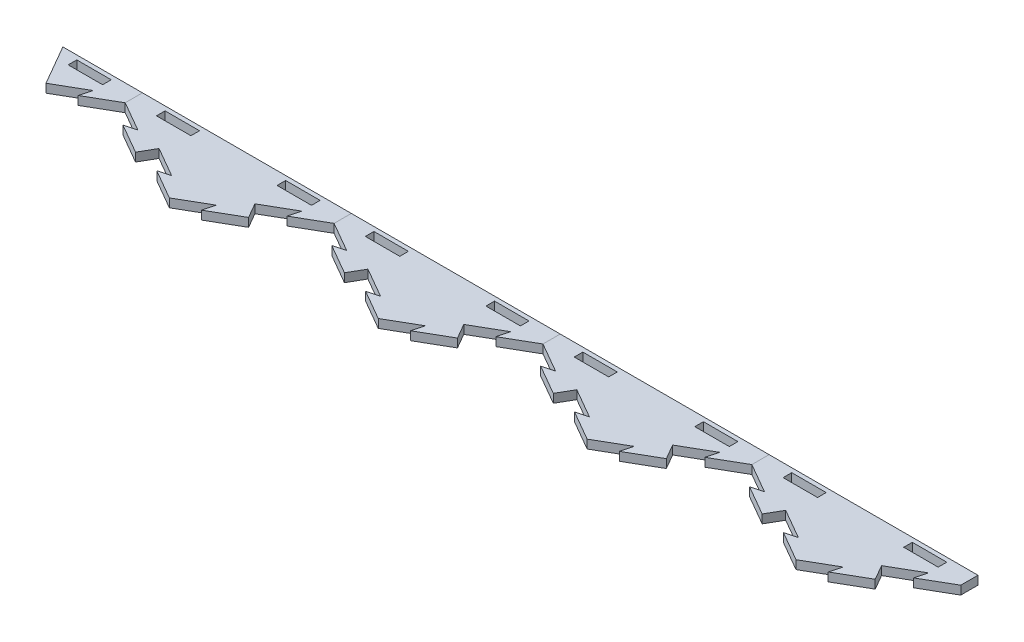
SolidWorks part; units mm, degrees
material "Cedar"
ref_plane "Front Plane" through (0, 0, 0) normal (0, 0, 1) x (1, 0, 0)
ref_plane "Top Plane" through (0, 0, 0) normal (0, 1, 0) x (1, 0, 0)
ref_plane "Right Plane" through (0, 0, 0) normal (1, 0, 0) x (0, 0, -1)
sketch "Sketch1" plane through (0, 0, 0) normal (0, 1, 0) x (1, 0, 0)
  line L0 (-76.9897, 0) -> (76.9897, 0) construction
  line L1 (-76.9897, 0) -> (0, -44.45)
  line L2 (0, -44.45) -> (76.9897, 0)
  line L3 (76.9897, 0) -> (76.9897, 88.9)
  line L4 (76.9897, 88.9) -> (0, 133.35)
  line L5 (0, 133.35) -> (-76.9897, 88.9)
  line L6 (-76.9897, 88.9) -> (-76.9897, 0)
  line L7 (0, -44.45) -> (0, 44.45) construction
  circle A0 centre (0, 44.45) radius 76.9897 construction
  point P9 (0, 0)
  dimension "D1" = 88.9
extrude "Boss-Extrude1" add sketch "Sketch1" against normal blind 6.35
sketch "Sketch2" plane through (0, 0, 0) normal (0, 1, 0) x (1, 0, 0)
  line L0 (-76.9897, 44.45) -> (76.9897, 44.45) construction
  line L1 (-76.9897, 88.9) -> (-76.9897, 0) construction
  line L2 (76.9897, 0) -> (76.9897, 88.9) construction
  point P2 (0, 44.45)
ref_axis "Axis1" through (0, 0, -44.45) along (0, 1, 0)
sketch "Sketch10" plane through (0, 0, 0) normal (0, 1, 0) x (1, 0, 0)
  line L0 (0, -44.45) -> (-21.997, -31.75) construction
  line L1 (-21.997, -31.75) -> (-13.3228, -29.4257)
  line L2 (-13.3228, -29.4257) -> (-35.3198, -16.7257)
  line L3 (-35.3198, -16.7257) -> (-38.4948, -22.225)
  line L4 (-21.997, -31.75) -> (-38.4948, -22.225)
  line L5 (-76.9897, 0) -> (0, -44.45) construction
  dimension "D1" = 45
  dimension "D2" = 6.35
extrude "Cut-Extrude4" cut sketch "Sketch10" against normal through all
sketch "Sketch11" plane through (0, 0, 0) normal (0, 1, 0) x (1, 0, 0)
  line L0 (-38.4948, -22.225) -> (-76.9897, 0) construction
  line L1 (-38.4948, -22.225) -> (-41.6698, -27.7243)
  line L2 (-41.6698, -27.7243) -> (-63.6669, -15.0243)
  line L3 (-63.6669, -15.0243) -> (-54.9926, -12.7)
  line L4 (-54.9926, -12.7) -> (-38.4948, -22.225)
  line L5 (-54.9926, -12.7) -> (-76.9897, 0) construction
  line L6 (-54.9926, -12.7) -> (-76.9897, 0) construction
  line L7 (-76.9897, 0) -> (-38.4948, -22.225) construction
  line L8 (-76.9897, 88.9) -> (-76.9897, 0) construction
  dimension "D1" = 45
  dimension "D2" = 6.35
extrude "Boss-Extrude4" add sketch "Sketch11" against normal blind 6.35
pattern_circular "CirPattern1" count 2 every 60 about axis through (0, 0, -44.45) along (0, 1, 0) of "Cut-Extrude4", "Boss-Extrude4"
sketch "Sketch12" plane through (0, 0, 0) normal (0, 1, 0) x (1, 0, 0)
  line L0 (-76.9897, 12.7) -> (76.9897, 12.7)
  line L1 (-76.9897, 88.9) -> (-76.9897, 0) construction
  line L2 (76.9897, 0) -> (76.9897, 88.9) construction
  line L3 (76.9897, 12.7) -> (76.9897, 133.35)
  line L4 (76.9897, 133.35) -> (-76.9897, 133.35)
  line L5 (-76.9897, 133.35) -> (-76.9897, 12.7)
  line L6 (0, 0) -> (0, 12.7) construction
  dimension "D1" = 12.7
extrude "Cut-Extrude5" cut sketch "Sketch12" against normal through all
sketch "Sketch13" plane through (0, 0, 0) normal (0, 1, 0) x (1, 0, 0)
  line L0 (0, 0) -> (0, 12.7) construction
  line L1 (-76.9897, 12.7) -> (76.9897, 12.7) construction
  line L2 (-44.45, 6.35) -> (44.45, 6.35) construction
  line L4 (-57.15, 9.525) -> (-31.75, 9.525)
  line L5 (-57.15, 9.525) -> (-57.15, 3.175)
  line L6 (-57.15, 3.175) -> (-31.75, 3.175)
  line L7 (-31.75, 9.525) -> (-31.75, 3.175)
  line L8 (-57.15, 9.525) -> (-31.75, 3.175) construction
  line L9 (-57.15, 3.175) -> (-31.75, 9.525) construction
  line L10 (31.75, 9.525) -> (57.15, 9.525)
  line L11 (31.75, 9.525) -> (31.75, 3.175)
  line L12 (31.75, 3.175) -> (57.15, 3.175)
  line L13 (57.15, 9.525) -> (57.15, 3.175)
  line L14 (31.75, 9.525) -> (57.15, 3.175) construction
  line L15 (31.75, 3.175) -> (57.15, 9.525) construction
  point P7 (0, 6.35)
  point P8 (0, 6.35)
  dimension "D1" = 6.35
  dimension "D2" = 25.4
  dimension "D3" = 6.35
  dimension "D4" = 25.4
  dimension "D5" = 88.9
extrude "Cut-Extrude6" cut sketch "Sketch13" against normal through all
pattern_linear "LPattern1" count 5 spacing 153.9793 along (1, 0, 0) count 2 spacing 153.9793 along (-1, 0, 0) pattern seed only yes of bodies 136 131
sketch "Sketch14" plane through (0, 0, 0) normal (0, 1, 0) x (1, 0, 0)
  line L0 (615.9173, -44.45) -> (615.9173, 12.7)
  line L1 (538.9276, 12.7) -> (692.9069, 12.7) construction
  line L2 (615.9173, 12.7) -> (692.9069, 12.7)
  line L3 (692.9069, 12.7) -> (692.9069, -44.45)
  line L4 (692.9069, -44.45) -> (615.9173, -44.45)
  line L5 (-153.9793, -44.45) -> (-153.9793, 12.7)
  line L6 (-230.969, 12.7) -> (-76.9897, 12.7) construction
  line L7 (-153.9793, 12.7) -> (-230.969, 12.7)
  line L8 (-230.969, 12.7) -> (-230.969, -44.45)
  line L9 (-230.969, -44.45) -> (-153.9793, -44.45)
  line L10 (580.5974, -16.7257) -> (597.5864, 12.7)
  line L11 (597.5864, 12.7) -> (615.9173, 12.7)
  line L12 (580.5974, -16.7257) -> (574.2474, -27.7243)
  line L13 (574.2474, -27.7243) -> (615.9173, -44.45)
  line L14 (-112.3095, -27.7243) -> (-135.6484, 12.7)
  line L15 (-135.6484, 12.7) -> (-153.9793, 12.7)
  line L16 (-112.3095, -27.7243) -> (-134.3065, -40.4243)
  line L17 (-134.3065, -40.4243) -> (-153.9793, -44.45)
  line L18 (-118.6595, -16.7257) -> (-112.3095, -27.7243) construction
  line M5 (673.0673, 9.525) -> (673.0673, 3.175)
  line M6 (673.0673, 3.175) -> (647.6673, 3.175)
  line M7 (647.6673, 3.175) -> (647.6673, 9.525)
  line M8 (647.6673, 9.525) -> (673.0673, 9.525)
  line M13 (692.9069, 12.7) -> (538.9276, 12.7)
  line M19 (580.5974, -16.7257) -> (602.5945, -29.4257)
  line M20 (602.5945, -29.4257) -> (593.9202, -31.75)
  line M21 (593.9202, -31.75) -> (615.9173, -44.45)
  line M22 (615.9173, -44.45) -> (637.9143, -31.75)
  line M23 (637.9143, -31.75) -> (635.5901, -40.4243)
  line M24 (635.5901, -40.4243) -> (657.5871, -27.7243)
  line M25 (657.5871, -27.7243) -> (651.2371, -16.7257)
  line M26 (651.2371, -16.7257) -> (673.2341, -4.0257)
  line M27 (673.2341, -4.0257) -> (670.9099, -12.7)
  line M28 (670.9099, -12.7) -> (692.9069, 0)
  line M29 (692.9069, 0) -> (692.9069, 12.7)
extrude "Cut-Extrude7" cut sketch "Sketch14" against normal through all contours L17 L16 L14 L15 L5 | L10 L0 M19 M20 M21 M13 | L0 M22 M23 M24 M25 M26 M27 M28 M29 M13 M8 M5 M6 M7 | L8 L9 L5 L7 region at (603.1355, 0, 12.4572) region at (644.4492, 0, 8.9256) region at (-192.4741, 0, 15.875) region at (-138.3884, 0, 16.3957)
sketch "Sketch15" plane through (0, 0, 0) normal (0, 1, 0) x (1, 0, 0)
  line L0 (538.9276, 12.7) -> (597.5864, 12.7)
  line L1 (597.5864, 12.7) -> (597.5864, -27.7243)
  line L2 (597.5864, -27.7243) -> (538.9276, -27.7243)
  line L3 (538.9276, -27.7243) -> (538.9276, 12.7)
extrude "Cut-Extrude8" cut sketch "Sketch15" against normal through all
